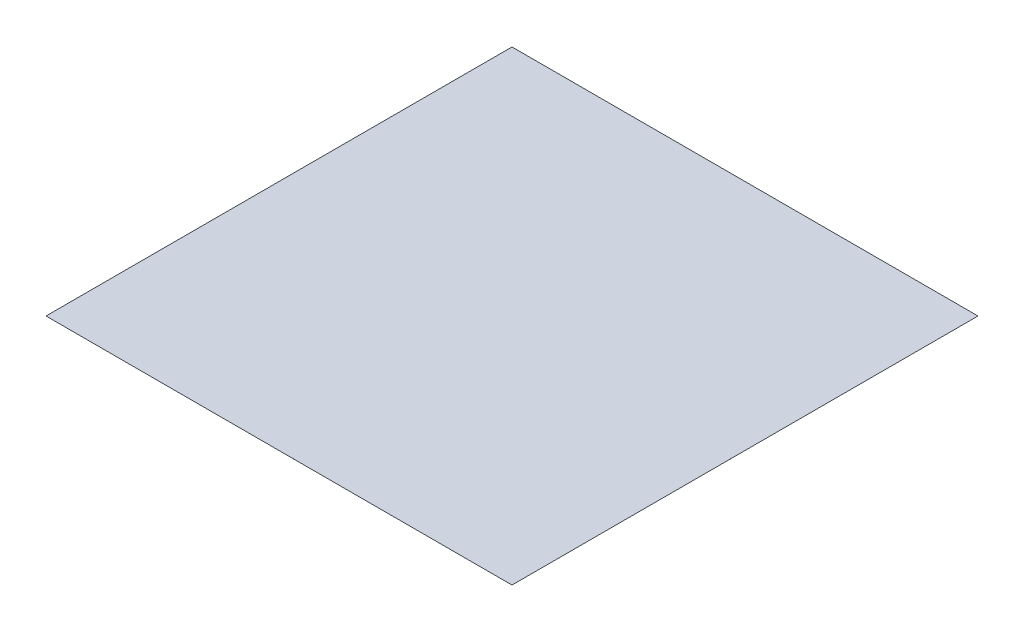
SolidWorks part; units mm, degrees
ref_plane "Front Plane" through (0, 0, 0) normal (0, 0, 1) x (1, 0, 0)
ref_plane "Top Plane" through (0, 0, 0) normal (0, 1, 0) x (1, 0, 0)
ref_plane "Right Plane" through (0, 0, 0) normal (1, 0, 0) x (0, 0, -1)
sketch "Sketch1" plane through (0, 0, 0) normal (0, 1, 0) x (1, 0, 0)
  line L1 (-2784, -2784) -> (2784, -2784)
  line L2 (-2784, -2784) -> (-2784, 2784)
  line L3 (-2784, 2784) -> (2784, 2784)
  line L4 (2784, -2784) -> (2784, 2784)
  line L5 (-2784, -2784) -> (2784, 2784) construction
  line L6 (-2784, 2784) -> (2784, -2784) construction
  point P0 (0, 0)
  dimension "D1" = 5568
extrude "Boss-Extrude1" add sketch "Sketch1" along normal blind 0.0045
ref_axis "Axis1" through (0, 0, 0) along (0, 1, 0)
